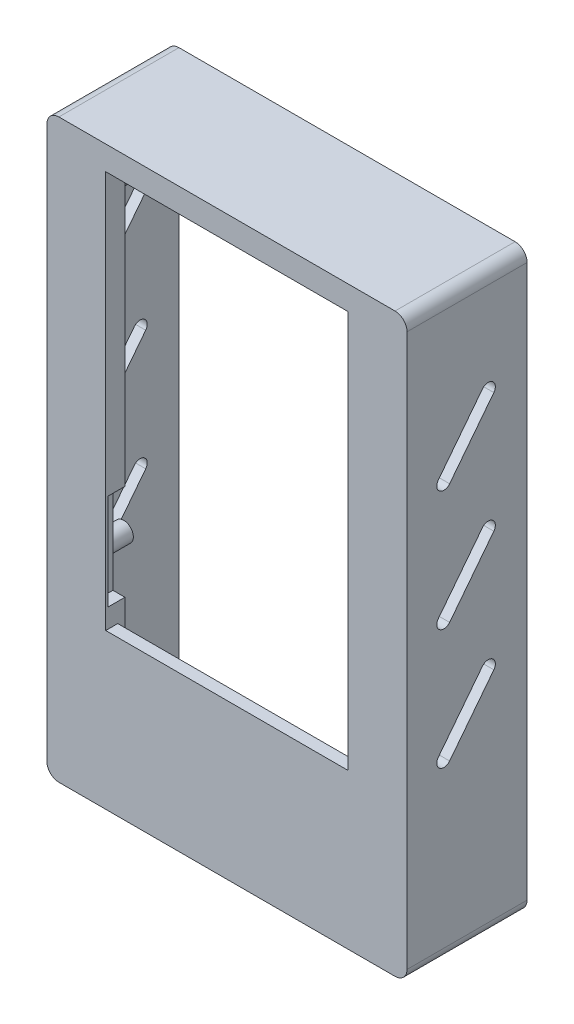
SolidWorks part; units mm, degrees
ref_plane "Plan de face" through (0, 0, 0) normal (0, 0, 1) x (1, 0, 0)
ref_plane "Plan de dessus" through (0, 0, 0) normal (0, 1, 0) x (1, 0, 0)
ref_plane "Plan de droite" through (0, 0, 0) normal (1, 0, 0) x (0, 0, -1)
sketch "Esquisse1" plane through (0, 0, 0) normal (0, 0, 1) x (1, 0, 0)
  line L1 (75, -120) -> (-75, -120)
  line L2 (75, -120) -> (75, 120)
  line L3 (75, 120) -> (-75, 120)
  line L4 (-75, -120) -> (-75, 120)
  line L5 (75, -120) -> (-75, 120) construction
  line L6 (75, 120) -> (-75, -120) construction
  point P0 (0, 0)
  dimension "D1" = 240
  dimension "D2" = 150
extrude "Boss.-Extru.1" add sketch "Esquisse1" along normal blind 50
sketch "Esquisse2" plane through (0, 0, 0) normal (0, 0, -1) x (-1, 0, 0)
  line L0 (-70, -110) -> (-70, 110)
  line L5 (-70, 110) -> (-67, 110)
  line L6 (-65, 112) -> (-65, 115)
  line L7 (-65, 115) -> (65, 115)
  line L8 (65, 115) -> (65, 112)
  line L9 (67, 110) -> (70, 110)
  line L10 (70, 110) -> (70, -110)
  line L13 (25, -115) -> (-65, -115)
  line L14 (-65, -115) -> (-65, -112)
  line L15 (-67, -110) -> (-70, -110)
  line L17 (70, -110) -> (26, -110)
  line L18 (25, -111) -> (25, -115)
  arc A0 (-65, -112) -> (-67, -110) centre (-67, -112) ccw
  arc A2 (65, 112) -> (67, 110) centre (67, 112) ccw
  arc A3 (-67, 110) -> (-65, 112) centre (-67, 112) ccw
  arc A4 (25, -111) -> (26, -110) centre (26, -111) cw
  point P0 (0, 0)
  point P20 (25, -110)
  point P29 (-65, 110)
  dimension "D7" = 2
  dimension "D10" = 1
  dimension "D1" = 5
  dimension "D2" = 5
  dimension "D3" = 5
  dimension "D4" = 5
  dimension "D5" = 5
  dimension "D6" = 5
  dimension "D8" = 45
  dimension "D9" = 10
extrude "Enlèv. mat.-Extru.1" cut sketch "Esquisse2" against normal blind 42
sketch "Esquisse3" plane through (0, 0, 50) normal (0, 0, 1) x (1, 0, 0)
  line L0 (-75, 120) -> (-50.5, 110)
  line L1 (50.5, -55.5) -> (-50.5, -55.5)
  line L2 (50.5, -55.5) -> (50.5, 110)
  line L3 (50.5, 110) -> (-50.5, 110)
  line L4 (-50.5, -55.5) -> (-50.5, 110)
  line L5 (50.5, -55.5) -> (-50.5, 110) construction
  line L6 (50.5, 110) -> (-50.5, -55.5) construction
  line L13 (50.5, 110) -> (75, 120)
  point P0 (0, 27.25)
  dimension "D1" = 165.5
  dimension "D2" = 101
  dimension "D4" = 10
extrude "Enlèv. mat.-Extru.2" cut sketch "Esquisse3" against normal through all contours L4 L1 L2 L3 region at (0, 27.25, 50)
fillet "Congé1" radius 5 4 edges at (75, -120, 25) (-75, -120, 25) (-75, 120, 25) (75, 120, 25)
sketch "Esquisse4" plane through (0, 0, 0) normal (0, 0, -1) x (-1, 0, 0)
  circle A0 centre (-70, 115) radius 2.8
  circle A1 centre (70, 115) radius 2.8
  circle A2 centre (70, -115) radius 2.8
  circle A3 centre (-70, -115) radius 2.8
  dimension "D1" = 5.6
extrude "Enlèv. mat.-Extru.3" cut sketch "Esquisse4" against normal blind 15
sketch "Esquisse5" plane through (75, 0, 0) normal (1, 0, 0) x (0, 0, -1)
  line L0 (-37, 55) -> (-18.5849, 78.683)
  line L1 (-13.8483, 75) -> (-32.2634, 51.317)
  line L2 (-37, 5) -> (-18.5849, 28.683)
  line L3 (-13.8483, 25) -> (-32.2634, 1.317)
  line L4 (-37, -45) -> (-18.5849, -21.317)
  line L5 (-13.8483, -25) -> (-32.2634, -48.683)
  arc A0 (-18.5849, 78.683) -> (-13.8483, 75) centre (-16.2166, 76.8415) cw
  arc A1 (-32.2634, 51.317) -> (-37, 55) centre (-34.6317, 53.1585) cw
  arc A2 (-18.5849, 28.683) -> (-13.8483, 25) centre (-16.2166, 26.8415) cw
  arc A3 (-32.2634, 1.317) -> (-37, 5) centre (-34.6317, 3.1585) cw
  arc A4 (-18.5849, -21.317) -> (-13.8483, -25) centre (-16.2166, -23.1585) cw
  arc A5 (-32.2634, -48.683) -> (-37, -45) centre (-34.6317, -46.8415) cw
  dimension "D2" = 3
  dimension "D1" = 30
  dimension "D3" = 13
  dimension "D4" = 60
  dimension "D5" = 40
  dimension "D6" = 50
  dimension "D7" = 50
extrude "Enlèv. mat.-Extru.4" cut sketch "Esquisse5" against normal through all
sketch "Esquisse6" plane through (0, 0, 42) normal (0, 0, -1) x (-1, 0, 0)
  line L0 (70, -110) -> (70, 110) construction
  line L1 (26, -110) -> (70, -110) construction
  circle A0 centre (-14.8, -79.8159) radius 2
  circle A1 centre (13, -105.0159) radius 2
  dimension "D1" = 4
  dimension "D2" = 27.8
  dimension "D3" = 25.2
  dimension "D4" = 57
  dimension "D5" = 4.9841
sketch "Esquisse7" plane through (0, 0, 42) normal (0, 0, -1) x (-1, 0, 0)
  circle A0 centre (-57, 105.8) radius 2.3
  circle A1 centre (-57, -51.3) radius 2.3
  circle A2 centre (57, 105.8) radius 2.3
  circle A3 centre (57, -51.3) radius 2.3
  dimension "D1" = 4.6
  dimension "D2" = 6.5
  dimension "D3" = 4.2
  dimension "D4" = 6.5
  dimension "D5" = 4.2
extrude "Enlèv. mat.-Extru.5" cut sketch "Esquisse7" against normal blind 5
extrude "Enlèv. mat.-Extru.6" cut sketch "Esquisse6" against normal blind 5
sketch "Esquisse8" plane through (0, 0, 42) normal (0, 0, -1) x (-1, 0, 0)
  line L0 (50.5, -47.5) -> (55.5, -47.5)
  line L1 (50.5, 110) -> (50.5, -55.5) construction
  line L2 (55.5, -47.5) -> (55.5, -7.5)
  line L3 (55.5, -7.5) -> (50.5, -7.5)
  line L4 (50.5, -7.5) -> (50.5, -47.5)
  dimension "D1" = 40
  dimension "D2" = 5
  dimension "D3" = 8
extrude "Enlèv. mat.-Extru.7" cut sketch "Esquisse8" against normal blind 7
sketch "Esquisse9" plane through (0, 0, 42) normal (0, 0, -1) x (-1, 0, 0)
  circle A0 centre (-60, 97) radius 4
  circle A1 centre (60, 97) radius 4
  circle A2 centre (60, -33) radius 4
  circle A3 centre (-60, -33) radius 4
  dimension "D1" = 8
  dimension "D2" = 9.5
  dimension "D3" = 13
  dimension "D4" = 120
  dimension "D5" = 130
extrude "Boss.-Extru.2" add sketch "Esquisse9" along normal blind 9
sketch "Esquisse10" plane through (0, 0, 33) normal (0, 0, -1) x (-1, 0, 0)
  circle A0 centre (-60, 97) radius 2.3
  circle A1 centre (60, 97) radius 2.3
  circle A2 centre (60, -33) radius 2.3
  circle A3 centre (-60, -33) radius 2.3
  dimension "D1" = 4.6
extrude "Enlèv. mat.-Extru.8" cut sketch "Esquisse10" against normal blind 8
sketch "Esquisse11" plane through (0, 0, 42) normal (0, 0, -1) x (-1, 0, 0)
  line L0 (-50.5, -55.5) -> (-50.5, -66.5)
  line L2 (50.5, -66.5) -> (50.5, -55.5)
  line L3 (50.5, -55.5) -> (-50.5, -55.5)
  line L4 (-50.5, -66.5) -> (50.5, -66.5)
  line L5 (-50.5, 110) -> (-50.5, -55.5) construction
  line L6 (50.5, 110) -> (50.5, -7.5) construction
  line L7 (50.5, -55.5) -> (-50.5, -55.5) construction
  dimension "D1" = 11
extrude "Enlèv. mat.-Extru.9" cut sketch "Esquisse11" against normal blind 3
sketch "Esquisse13" plane through (0, 0, 42) normal (0, 0, -1) x (-1, 0, 0)
  circle A0 centre (-14.8, -79.8159) radius 4
  circle A1 centre (13, -105.0159) radius 4
  circle A2 centre (-14.8, -79.8159) radius 2.3
  circle A3 centre (13, -105.0159) radius 2
  dimension "D1" = 8
  dimension "D2" = 4.6
extrude "Boss.-Extru.3" add sketch "Esquisse13" along normal blind 10 contours A0 | A2 | A1 | A3
sketch "Esquisse14" plane through (0, -110, 0) normal (0, 1, 0) x (1, 0, 0)
  circle A0 centre (-63.6276, -37.7) radius 2.3
  circle A1 centre (-63.6276, -4.8) radius 2.3
  circle A2 centre (-20.3276, -4.8) radius 2.3
  dimension "D1" = 4.6
  dimension "D2" = 43.3
  dimension "D3" = 32.9
  dimension "D4" = 4.8
extrude "Enlèv. mat.-Extru.10" cut sketch "Esquisse14" against normal blind 6.7
